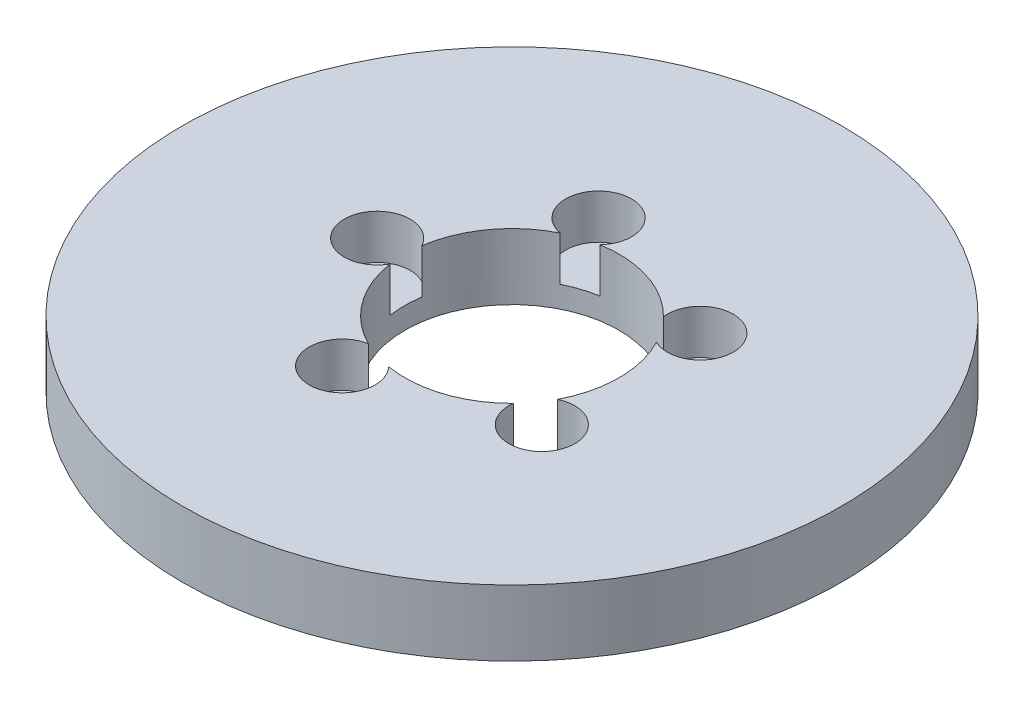
SolidWorks part; units mm, degrees
ref_plane "Front Plane" through (0, 0, 0) normal (0, 0, 1) x (1, 0, 0)
ref_plane "Top Plane" through (0, 0, 0) normal (0, 1, 0) x (1, 0, 0)
ref_plane "Right Plane" through (0, 0, 0) normal (1, 0, 0) x (0, 0, -1)
sketch "Sketch1" plane through (0, 0, 0) normal (0, 1, 0) x (1, 0, 0)
  circle A0 centre (0, 0) radius 100
  dimension "FLANGE_OD" = 200
extrude "Boss-Extrude1" add sketch "Sketch1" along normal blind 20
sketch "Sketch2" plane through (0, 0, 0) normal (0, 1, 0) x (1, 0, 0)
  circle A0 centre (0, 0) radius 32.5
  dimension "BORE_D" = 65
extrude "Cut-Extrude1" cut sketch "Sketch2" along normal through all
sketch "Sketch3" plane through (0, 20, 0) normal (0, 1, 0) x (1, 0, 0)
  circle A0 centre (0, 0) radius 40.9141 construction
  circle A1 centre (-40.9141, 0) radius 10
  dimension "BOLT_D" = 20
  dimension "BOLT_PCD" = 81.8282
extrude "Cut-Extrude2" cut sketch "Sketch3" against normal blind 13.4739
pattern_circular "CirPattern1" count 5 over 360 about axis through (0, 0, 0) along (0, 1, 0) of "Cut-Extrude2"
